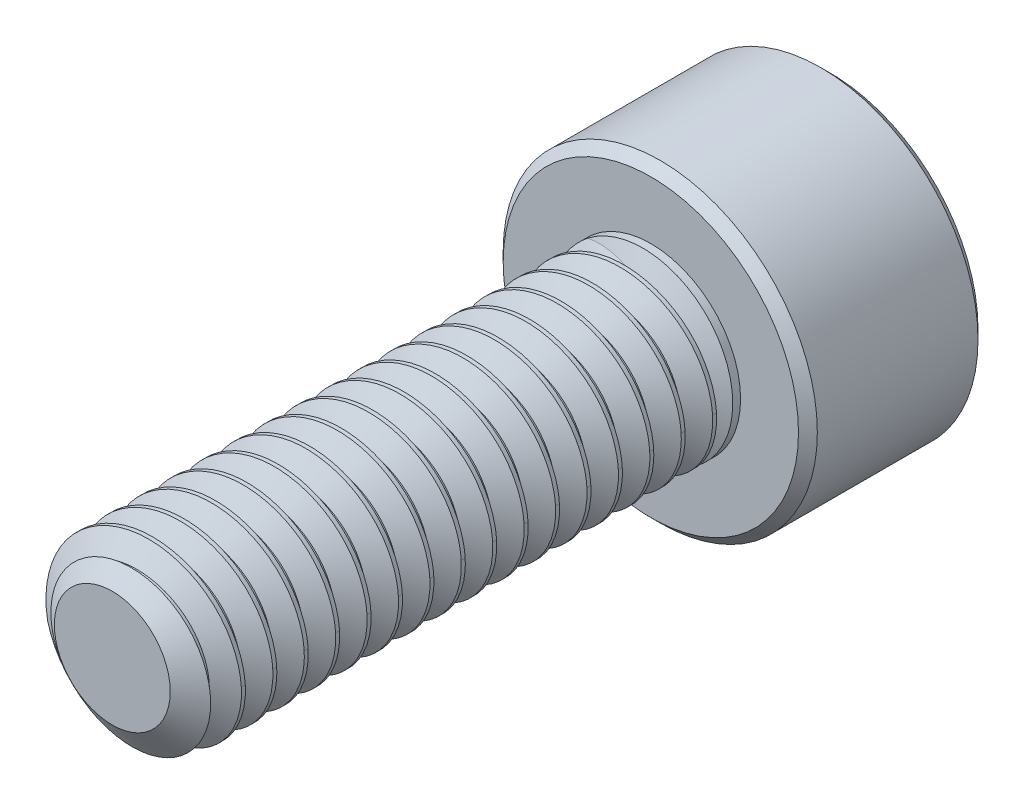
SolidWorks part; units mm, degrees
ref_plane "Front Plane" through (0, 0, 0) normal (0, 0, 1) x (1, 0, 0)
ref_plane "Top Plane" through (0, 0, 0) normal (0, 1, 0) x (1, 0, 0)
ref_plane "Right Plane" through (0, 0, 0) normal (1, 0, 0) x (0, 0, -1)
sketch "Sketch1" plane through (0, 0, 0) normal (0, 0, 1) x (1, 0, 0)
  circle A0 centre (0, 0) radius 2
  dimension "OD" = 4
extrude "Extrude1" add sketch "Sketch1" against normal blind 12
sketch "Sketch2" plane through (0, 0, 0) normal (0, 0, 1) x (1, 0, 0)
  circle A0 centre (0, 0) radius 2 construction
  circle A1 centre (0, 0) radius 2
curve "Helix/Spiral1" pitch 0.7 height 12.7 turns 18.1429 parameters "pitch"=0.7
sketch "Sketch3" plane through (0, 0, 0) normal (1, 0, 0) x (0, 0, -1)
  line L0 (-0.6125, 2) -> (-0.35, 1.5453)
  line L1 (-0.35, 1.5453) -> (-0.2625, 1.5453)
  line L2 (-0.2625, 1.5453) -> (0, 2)
  line L3 (-0.6125, 2) -> (0, 2)
  line L4 (-0.3063, 2) -> (-0.3063, 1.5453) construction
  line L5 (-0.4813, 1.7727) -> (-0.1313, 1.7727) construction
  line L6 (0, 2) -> (0, -2) construction
  line L7 (0, -2) -> (12, -2) construction
  point P11 (3.15, -2)
  dimension "D1" = 0.0875
  dimension "D2" = 0.35
  dimension "D3" = 60
  dimension "D4" = 3.15
sweep "Cut-Sweep1" cut profiles "Sketch3" path "Helix/Spiral1"
sketch "Sketch4" plane through (0, 0, 0) normal (1, 0, 0) x (0, 0, -1)
  line L0 (0.4962, 2) -> (0, 1.2913)
  line L1 (0, 1.2913) -> (0, 2)
  line L2 (0.4962, 2) -> (0, 2)
  line L3 (-0.6125, 2) -> (0, 2) construction
  line L4 (0, 0) -> (7.0209, 0) construction
  dimension "D1" = 55
  dimension "D2" = 0.254
revolve "Cut-Revolve1" cut sketch "Sketch4" angle 360 about L4
sketch "Sketch5" plane through (0, 0, 0) normal (1, 0, 0) x (0, 0, -1)
  line L0 (12, -0.9741) -> (12, 1.9864) construction
  line L1 (12, 2) -> (0.1203, 2)
  line L2 (12, 2) -> (12, 0)
  line L3 (12, 0) -> (0.0001, 0)
  line L4 (0.0001, 1.6698) -> (0.0001, 0)
  line L5 (0.1203, 2) -> (0.0001, 1.6698)
  line L6 (0, 0) -> (9.9695, 0) construction
  point P3 (0.0001, 2)
  point P10 (0.0001, 2)
  dimension "D1" = 0.3302
  dimension "Thread min" = 0.0001
  dimension "D3" = 20
revolve "partially thread" [suppressed] add sketch "Sketch5" angle 360 about L6
sketch "Sketch6" plane through (0, 0, -12) normal (0, 0, -1) x (-1, 0, 0)
  circle A0 centre (0, 0) radius 3.5
  dimension "head dia" = 7
extrude "Extrude2" add sketch "Sketch6" along normal blind 4
sketch "Sketch7" plane through (0, 0, -16) normal (0, 0, -1) x (-1, 0, 0)
  line L1 (0, 1.7321) -> (-1.5, 0.866)
  line L2 (-1.5, 0.866) -> (-1.5, -0.866)
  line L3 (-1.5, -0.866) -> (0, -1.7321)
  line L4 (0, -1.7321) -> (1.5, -0.866)
  line L5 (1.5, -0.866) -> (1.5, 0.866)
  line L6 (1.5, 0.866) -> (0, 1.7321)
  circle A0 centre (0, 0) radius 1.5 construction
  dimension "hex dia" = 3
extrude "Cut-Extrude1" cut sketch "Sketch7" against normal blind 2.25
sketch "Sketch8" plane through (0, 0, -16) normal (0, 0, -1) x (-1, 0, 0)
  circle A0 centre (0, 0) radius 1.7321
extrude "Cut-Extrude2" cut sketch "Sketch8" against normal through all draft 45
chamfer "Chamfer1" distance 0.21 angle 45 2 edges at (-3.5, 0, -16) (-3.5, 0, -12)
sketch "Sketch9" plane through (0, 0, 0) normal (1, 0, 0) x (0, 0, -1)
  line L0 (0, 2) -> (0, -2) construction
  line L1 (3.85, 2) -> (3.85, -2) construction
  dimension "D1" = 3.85
sketch "Sketch10" plane through (0, 0, 0) normal (1, 0, 0) x (0, 0, -1)
  line L0 (12, 2) -> (12, 0)
  line L1 (12, 2) -> (11.825, 2)
  line L2 (11.825, 2) -> (10.9966, 0)
  line L3 (12, 0) -> (10.9966, 0)
  line L4 (12, 3.29) -> (12, -3.29) construction
  dimension "D1" = 22.5
  dimension "D2" = 0.175
revolve "Revolve1" add sketch "Sketch10" angle 360 about L3
equation "\"D3@Helix/Spiral1\" = \"screw length@Extrude1\"+\"pitch@Helix/Spiral1\""
equation "\"D1@Sketch3\" = \"pitch@Helix/Spiral1\"*.125"
equation "\"D2@Sketch3\" = \"pitch@Helix/Spiral1\"*.5"
equation "\"D1@Cut-Extrude1\" = \"hex dia@Sketch7\"*.75"
equation "\"D1@Chamfer1\" = \"head dia@Sketch6\"*.03"
equation "\"D1@Sketch9\" = \"pitch@Helix/Spiral1\"*5.5"
equation "\"D2@Sketch10\" = \"pitch@Helix/Spiral1\"*.25"
equation "\"D4@Sketch3\" = \"pitch@Helix/Spiral1\"*4.50"
